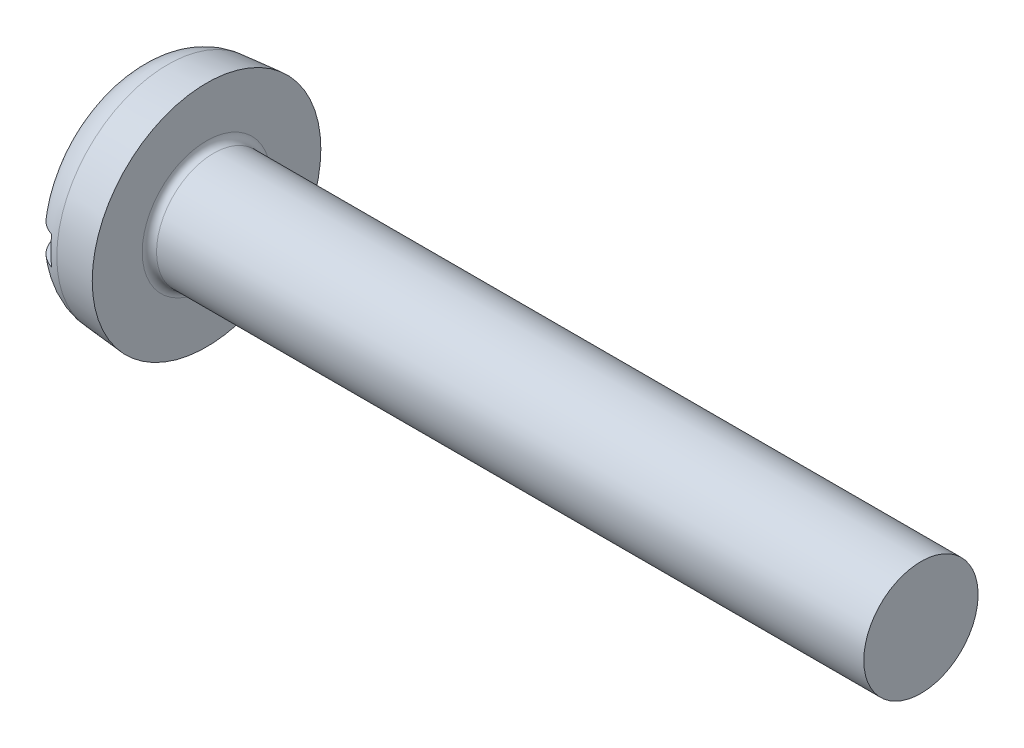
SolidWorks part; units mm, degrees
ref_plane "Front Plane" through (0, 0, 0) normal (0, 0, 1) x (1, 0, 0)
ref_plane "Top Plane" through (0, 0, 0) normal (0, 1, 0) x (1, 0, 0)
ref_plane "Right Plane" through (0, 0, 0) normal (1, 0, 0) x (0, 0, -1)
sketch "BodySke" plane through (0, 0, 0) normal (0, 0, 1) x (1, 0, 0)
  line L0 (0, 0) -> (19.6365, 0) construction
  line L1 (0, 0) -> (0, 1.5125)
  line L2 (0, 1.5125) -> (1, 1.6)
  line L3 (1, 1.6) -> (1, 0.8)
  line L4 (1, 0.8) -> (11, 0.8)
  line L5 (11, 0.8) -> (11, 0)
  line L6 (11, 0) -> (0, 0)
  line L7 (10.65, 0) -> (10.65, 0.8) construction
  line L8 (1, 0) -> (1, 0.8) construction
  point P12 (11, 0.601)
  dimension "Thread_minor" = 1.202
  dimension "Thread_length" = 10
  dimension "Advance" = 0.35
revolve "BaseBody" add sketch "BodySke" angle 360 about L0
cosmetic thread "ThreadCosmetic" [suppressed] parameters "Thread_length"=10, "Thread_minor"=1.202
fillet "Fillet1" radius 0.1 1 edges at (1, 0, 0.8)
fillet "Head_Radius" radius 0.5 1 edges at (0, 0, 1.5125)
sketch "SlotSke" plane through (0, 0, 0) normal (1, 0, 0) x (0, 0, -1)
  line L0 (-1.6, 0.2) -> (1.6, -0.2) construction
  line L1 (-1.6, 0.2) -> (1.6, 0.2)
  line L2 (-1.6, 0.2) -> (-1.6, -0.2)
  line L3 (-1.6, -0.2) -> (1.6, -0.2)
  line L4 (1.6, 0.2) -> (1.6, -0.2)
  dimension "D1" = 3.2
extrude "Slot" cut sketch "SlotSke" along normal blind 0.35
sketch "ThdSchSke" plane through (0, 0, 0) normal (0, 0, 1) x (1, 0, 0)
  line L0 (10.8851, 1.0298) -> (10.8851, 0.8)
  line L1 (10.8851, 1.0298) -> (11.1149, 1.0298)
  line L2 (11.1149, 1.0298) -> (11.1149, 0.8)
  line L3 (11.1149, 0.8) -> (11, 0.601)
  line L4 (11, 0.601) -> (10.8851, 0.8)
  line L5 (1, 0.8) -> (11, 0.8) construction
  line L6 (0, 0) -> (12.5247, 0) construction
  line L7 (0, 0) -> (19.6365, 0) construction
revolve "ThreadSchematic" [suppressed] cut sketch "ThdSchSke" angle 360 about L6
pattern_linear "ThdSchPat" [suppressed] of bodies 115
equation "\"Thread_minor@ThreadCosmetic\" = \"Thread_minor@BodySke\""
equation "\"Thread_length@ThreadCosmetic\" = \"Thread_length@BodySke\""
equation "\"D1@SlotSke\" = \"Head_diameter@BodySke\""
equation "\"Advance@ThdSchPat\" = \"Advance@BodySke\""
equation "\"Tooth_Num@ThdSchPat\" =  int( \"Thread_length@BodySke\" / \"Advance@BodySke\" ) "
